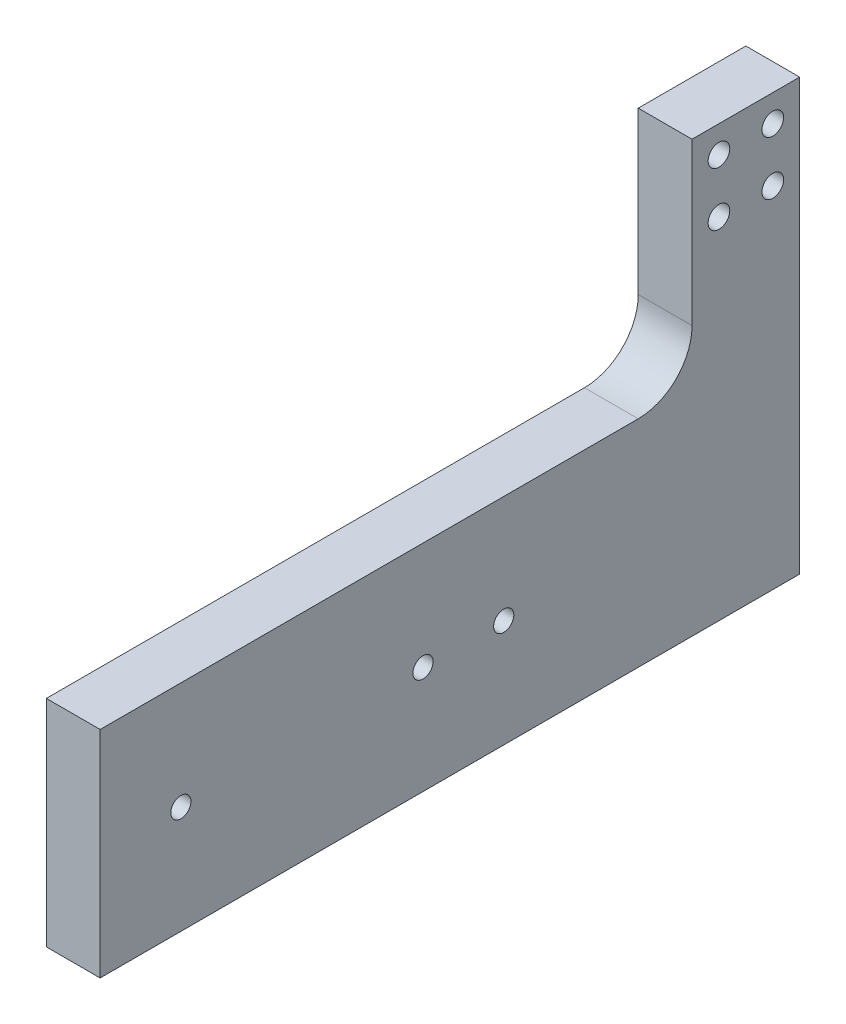
SolidWorks part; units mm, degrees
material "6061-T6 (SS)"
ref_plane "Front Plane" through (0, 0, 0) normal (0, 0, 1) x (1, 0, 0)
ref_plane "Top Plane" through (0, 0, 0) normal (0, 1, 0) x (1, 0, 0)
ref_plane "Right Plane" through (0, 0, 0) normal (1, 0, 0) x (0, 0, -1)
sketch "Sketch1" plane through (0, 0, 0) normal (1, 0, 0) x (0, 0, -1)
  line L0 (0, 0) -> (0, 101.6)
  line L1 (0, 101.6) -> (-25.4, 101.6)
  line L2 (-25.4, 101.6) -> (-25.4, 50.8)
  line L3 (-25.4, 50.8) -> (-165.1, 50.8)
  line L4 (-165.1, 50.8) -> (-165.1, 0)
  line L5 (-165.1, 0) -> (0, 0)
  line L6 (-69.85, 25.4) -> (-146.05, 25.4) construction
  circle A0 centre (-146.05, 25.4) radius 2.3813
  circle A1 centre (-88.9, 25.4) radius 2.3813
  circle A2 centre (-69.85, 25.4) radius 2.3813
  dimension "D5" = 4.7625
  dimension "D1" = 101.6
  dimension "D2" = 165.1
  dimension "D3" = 50.8
  dimension "D4" = 25.4
  dimension "D6" = 19.05
  dimension "D7" = 76.2
  dimension "D8" = 95.25
  dimension "D9" = 25.4
extrude "Boss-Extrude1" add sketch "Sketch1" along normal blind 12.7
hole_wizard "#10 Clearance Hole1" positions "Sketch2" profile "Sketch3" hole size "#10" standard "ANSI Inch" end condition through all
sketch "Sketch2" plane through (12.7, 0, 0) normal (1, 0, 0) x (0, 0, -1)
  line L0 (-25.4, 101.6) -> (-25.4, 50.8) construction
  line L1 (0, 0) -> (0, 101.6) construction
  point P0 (-19.05, 95.25)
  point P2 (-6.35, 95.25)
  point P4 (-6.35, 82.55)
  point P6 (-19.05, 82.55)
  dimension "D1" = 6.35
  dimension "D2" = 6.35
  dimension "D3" = 6.35
  dimension "D4" = 6.35
  dimension "D5" = 12.7
  dimension "D6" = 12.7
  dimension "D7" = 6.35
  dimension "D8" = 6.35
sketch "Sketch3" plane through (12.7, 95.25, 19.05) normal (0, 1, 0) x (0, 0, -1)
  line L0 (0, 0) -> (0, 12.7)
  line L1 (0, 12.7) -> (2.5527, 12.7)
  line L2 (2.5527, 12.7) -> (2.5527, 0)
  line L5 (2.5527, 0) -> (0, 0)
  line L11 (0, -6.35) -> (0, 107.95) construction
  dimension "Thru Hole Dia." = 5.1054
  dimension "Thru Hole Depth" = 12.7
ref_point "Point1"
ref_point "Point2"
ref_point "Point3"
fillet "Fillet1" radius 12.7 1 edges at (6.35, 50.8, 25.4)
